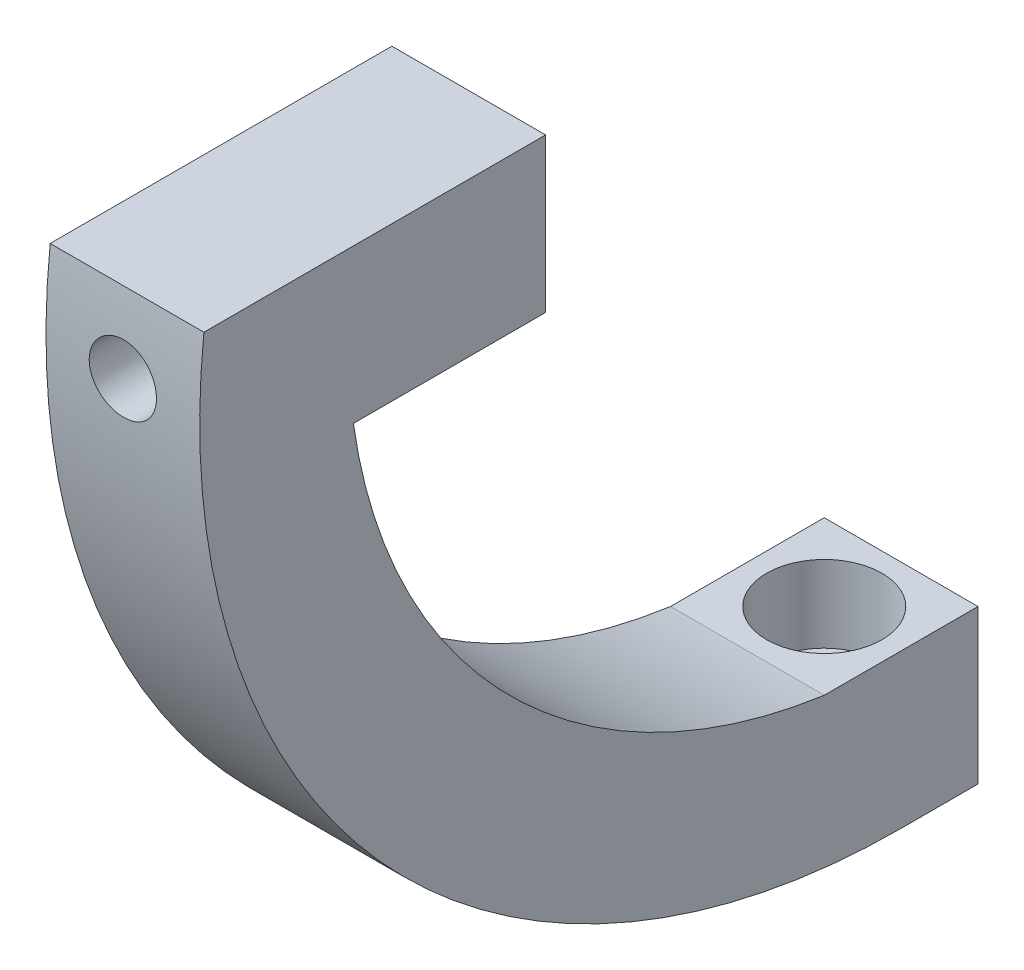
SolidWorks part; units mm, degrees
ref_plane "Front Plane" through (0, 0, 0) normal (0, 0, 1) x (1, 0, 0)
ref_plane "Top Plane" through (0, 0, 0) normal (0, 1, 0) x (1, 0, 0)
ref_plane "Right Plane" through (0, 0, 0) normal (1, 0, 0) x (0, 0, -1)
ref_axis "Z" through (0, 0, 22.75) along (0, 0, -1)
sketch "Sketch4" plane through (0, 0, 0) normal (0, 0, 1) x (1, 0, 0)
  circle A0 centre (0, 0) radius 17.5 construction
  dimension "D1" = 35
sketch "Sketch5" plane through (0, 0, 0) normal (1, 0, 0) x (0, 0, -1)
  line L0 (-18.5, 4) -> (-18.5, 0)
  line L1 (-18.5, 0) -> (-18.5, -4)
  line L2 (-26.5, -1.9833) -> (-26.5, 4) construction
  line L6 (-26.5, 4) -> (-18.5, 4)
  line L12 (-22.75, 0) -> (-13.0351, 0) construction
  line L13 (0, -36.0144) -> (0, 10.0185) construction
  line L14 (0, 0) -> (7.0065, 0) construction
  line L15 (0, -28.5) -> (-4, -28.5)
  line L16 (4, -28.5) -> (0, -28.5)
  line L17 (0, -36.5) -> (4, -36.5)
  line L18 (4, -36.5) -> (4, -28.5)
  line L19 (-36.2802, 4) -> (-36.2802, -4) construction
  line L20 (-36.2802, -4) -> (-28.5, -4) construction
  line L21 (-36.2802, 4) -> (-26.5, 4)
  line L22 (-28.5, -4) -> (-18.5, -4)
  circle A0 centre (0, 0) radius 17.5 construction
  arc A3 (-28.5, -4) -> (-4, -28.5) centre (0, 0) ccw
  arc A4 (-36.2802, 4) -> (0, -36.5) centre (0, 0) ccw
  point P2 (9.4307, -21)
  point P4 (0, -2.1363)
  dimension "D1" = 35
  dimension "D4" = 4
  dimension "D3" = 8
  dimension "D5" = 18.5
  dimension "D2" = 28.5
sketch "Sketch6" plane through (0, 0, 0) normal (0, 1, 0) x (1, 0, 0)
  circle A0 centre (0, 0) radius 17.5 construction
  dimension "D1" = 35
extrude "Boss-Extrude1" add sketch "Sketch5" along normal blind 4 and the other way blind 4
sketch "Sketch7" plane through (0, 0, 0) normal (0, 0, 1) x (1, 0, 0)
  circle A0 centre (0, 0) radius 1.75
  dimension "D1" = 3.5
extrude "Cut-Extrude1" cut sketch "Sketch7" along normal through all
sketch "Sketch8" plane through (0, 0, 0) normal (0, 1, 0) x (1, 0, 0)
  circle A0 centre (0, 0) radius 1.75
  dimension "D1" = 3.5
extrude "Cut-Extrude2" cut sketch "Sketch8" against normal through all
ref_axis "Y" through (0, -9.3489, 0) along (0, -1, 0)
sketch "Sketch9" plane through (0, -28.5, 0) normal (0, 1, 0) x (1, 0, 0)
  circle A0 centre (0, 0) radius 3
  dimension "D1" = 6
extrude "Cut-Extrude4" cut sketch "Sketch9" against normal blind 4
sketch "Sketch10" plane through (0, 0, 18.5) normal (0, 0, -1) x (-1, 0, 0)
  circle A0 centre (0, 0) radius 3
  dimension "D1" = 6
extrude "Cut-Extrude5" cut sketch "Sketch10" against normal blind 4
equation "\"rbracket-width\"= \"L2Thickness\""
equation "\"EyeCaptureRadius\"= ( \"EyeDiameter\" + \"EyeClearance\" ) / 2"
equation "\"rbracket_planetocenterline_dist\"= \"BasePlaneDistance\""
equation "\"EyeDiameter\" = 35"
equation "\"BasePlaneDistance\" = \"EyeDiameter\"/2+19.84"
equation "\"EyeClearance\" = 2"
equation "\"D1@Sketch4\"=\"EyeDiameter\""
equation "\"D1@Sketch6\"=\"EyeDiameter\""
equation "\"D1@Boss-Extrude1\"=\"rbracket-width\"/2"
equation "\"D2@Boss-Extrude1\"=\"rbracket-width\"/2"
equation "\"L2Thickness\" = 8"
equation "\"D3@Sketch5\"=\"L2Thickness\""
equation "\"D5@Sketch5\"=(\"EyeDiameter\"+\"EyeClearance\")/2"
equation "\"D1@Sketch5\"=\"EyeDiameter\""
equation "\"D2@Sketch5\"=(\"EyeDiameter\"+\"EyeClearance\")/2 + \"EyeClearance\" + \"L2Thickness\""
